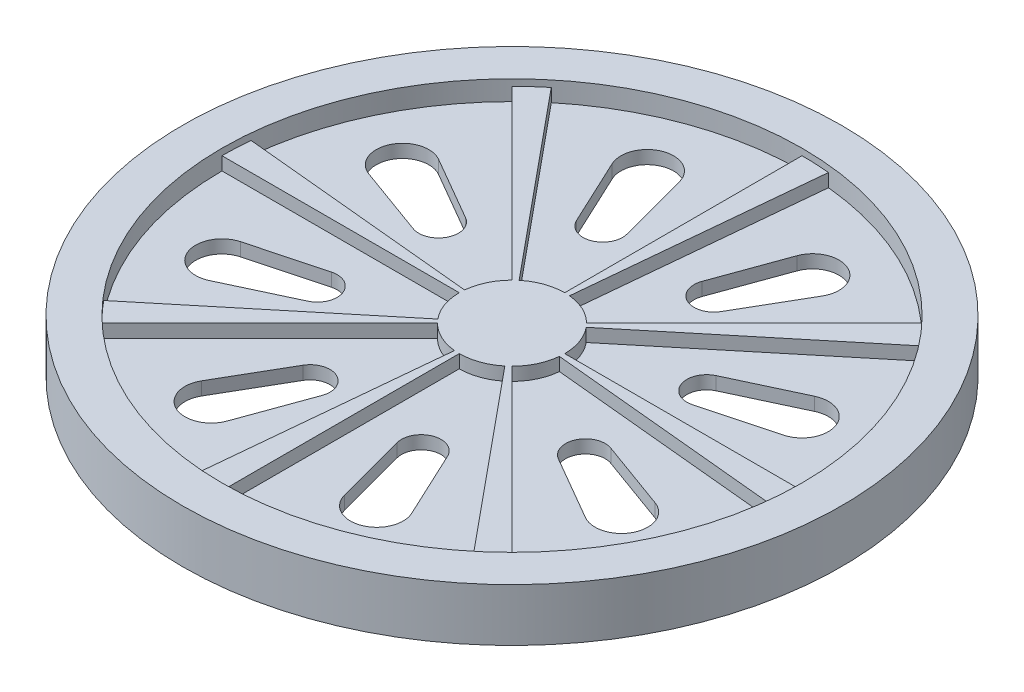
SolidWorks part; units mm, degrees
ref_plane "Front Plane" through (0, 0, 0) normal (0, 0, 1) x (1, 0, 0)
ref_plane "Top Plane" through (0, 0, 0) normal (0, 1, 0) x (1, 0, 0)
ref_plane "Right Plane" through (0, 0, 0) normal (1, 0, 0) x (0, 0, -1)
sketch "Sketch1" plane through (0, 0, 0) normal (0, 1, 0) x (1, 0, 0)
  line L0 (0, 4) -> (0, 22)
  line L1 (0.3831, 3.9816) -> (2.107, 21.8989)
  line L2 (3.0863, 2.5445) -> (16.9747, 13.995)
  line L3 (2.8284, 2.8284) -> (15.5563, 15.5563)
  line L4 (4, 0) -> (22, 0)
  line L5 (2.8284, -2.8284) -> (15.5563, -15.5563)
  line L6 (0, -4) -> (0, -22)
  line L7 (-2.8284, -2.8284) -> (-15.5563, -15.5563)
  line L8 (-4, 0) -> (-22, 0)
  line L9 (-2.8284, 2.8284) -> (-15.5563, 15.5563)
  line L10 (3.9816, -0.3831) -> (21.8989, -2.107)
  line L11 (2.5445, -3.0863) -> (13.995, -16.9747)
  line L12 (-0.3831, -3.9816) -> (-2.107, -21.8989)
  line L13 (-3.0863, -2.5445) -> (-16.9747, -13.995)
  line L14 (-3.9816, 0.3831) -> (-21.8989, 2.107)
  line L15 (-2.5445, 3.0863) -> (-13.995, 16.9747)
  line L17 (3.4591, 10.9535) -> (5.3757, 16.2376)
  line L18 (6.1674, 9.6906) -> (8.9833, 14.5554)
  line L20 (10.1912, 5.2993) -> (15.2829, 7.6806)
  line L21 (11.2133, 2.4913) -> (16.6444, 3.94)
  line L22 (10.9535, -3.4591) -> (16.2376, -5.3757)
  line L23 (9.6906, -6.1674) -> (14.5554, -8.9833)
  line L24 (5.2993, -10.1912) -> (7.6806, -15.2829)
  line L25 (2.4913, -11.2133) -> (3.94, -16.6444)
  line L26 (-3.4591, -10.9535) -> (-5.3757, -16.2376)
  line L27 (-6.1674, -9.6906) -> (-8.9833, -14.5554)
  line L28 (-10.1912, -5.2993) -> (-15.2829, -7.6806)
  line L29 (-11.2133, -2.4913) -> (-16.6444, -3.94)
  line L30 (-10.9535, 3.4591) -> (-16.2376, 5.3757)
  line L31 (-9.6906, 6.1674) -> (-14.5554, 8.9833)
  line L32 (-5.2993, 10.1912) -> (-7.6806, 15.2829)
  line L33 (-2.4913, 11.2133) -> (-3.94, 16.6444)
  circle A0 centre (0, 0) radius 25
  circle A1 centre (0, 0) radius 22
  circle A2 centre (0, 0) radius 4
  arc A3 (8.9833, 14.5554) -> (5.3757, 16.2376) centre (7.254, 15.5563) ccw
  arc A4 (3.4591, 10.9535) -> (6.1674, 9.6906) centre (4.8692, 10.442) ccw
  arc A5 (16.6444, 3.94) -> (15.2829, 7.6806) centre (16.1294, 5.8706) ccw
  arc A6 (10.1912, 5.2993) -> (11.2133, 2.4913) centre (10.8267, 3.9406) ccw
  arc A7 (14.5554, -8.9833) -> (16.2376, -5.3757) centre (15.5563, -7.254) ccw
  arc A8 (10.9535, -3.4591) -> (9.6906, -6.1674) centre (10.442, -4.8692) ccw
  arc A9 (3.94, -16.6444) -> (7.6806, -15.2829) centre (5.8706, -16.1294) ccw
  arc A10 (5.2993, -10.1912) -> (2.4913, -11.2133) centre (3.9406, -10.8267) ccw
  arc A11 (-8.9833, -14.5554) -> (-5.3757, -16.2376) centre (-7.254, -15.5563) ccw
  arc A12 (-3.4591, -10.9535) -> (-6.1674, -9.6906) centre (-4.8692, -10.442) ccw
  arc A13 (-16.6444, -3.94) -> (-15.2829, -7.6806) centre (-16.1294, -5.8706) ccw
  arc A14 (-10.1912, -5.2993) -> (-11.2133, -2.4913) centre (-10.8267, -3.9406) ccw
  arc A15 (-14.5554, 8.9833) -> (-16.2376, 5.3757) centre (-15.5563, 7.254) ccw
  arc A16 (-10.9535, 3.4591) -> (-9.6906, 6.1674) centre (-10.442, 4.8692) ccw
  arc A17 (-3.94, 16.6444) -> (-7.6806, 15.2829) centre (-5.8706, 16.1294) ccw
  arc A18 (-5.2993, 10.1912) -> (-2.4913, 11.2133) centre (-3.9406, 10.8267) ccw
  point P19 (0, 0)
  point P24 (0, 0)
  point P43 (0, 0)
  point P94 (0, 0)
  dimension "D1" = 50
  dimension "D2" = 8
  dimension "D5" = 8
  dimension "D4" = 8
extrude "Boss-Extrude2" add sketch "Sketch1" along normal blind 2 and the other way blind 2 contours A1 | A0
extrude "Boss-Extrude3" add sketch "Sketch1<5>" along normal blind 1.5 and the other way blind 1.5 contours A2 L1 A1 L0 | A2 L2 A1 L3 | A2 L10 A1 L4 | A2 L15 A1 L9 | A2 | A2 L14 A1 L8 | A2 L13 A1 L7 | A2 L12 A1 L6 | A2 L11 A1 L5 region at (0.7225, 0, -15.0538) region at (0, 0, 0) region at (-10.1337, 0, -11.1556) region at (11.1556, 0, -10.1337) region at (-15.0538, 0, -0.7225) region at (15.0538, 0, 0.7225) region at (-11.1556, 0, 10.1337) region at (10.1337, 0, 11.1556) region at (-0.7225, 0, 15.0538)
sketch "Sketch1<5>" plane through (0, 0, 0) normal (0, 1, 0) x (1, 0, 0) same geometry as "Sketch1"
extrude "Boss-Extrude5" add sketch "Sketch1<7>" along normal blind 0.5 and the other way blind 0.5 contours A2 L3 A1 L1 A4 L17 A3 L18 | A2 L0 A1 L15 A18 L32 A17 L33 | A2 L9 A1 L14 A16 L30 A15 L31 | A2 L8 A1 L13 A14 L28 A13 L29 | A2 L7 A1 L12 A12 L26 A11 L27 | A2 L5 A1 L10 A8 L22 A7 L23 | A2 L6 A1 L11 A10 L24 A9 L25 | A2 L4 A1 L2 A6 L20 A5 L21 region at (-1.4313, 0, -3.9861) region at (1.4876, 0, -12.9169) region at (-3.8383, 0, -1.8101) region at (10.1802, 0, -8.0882) region at (-3.9861, 0, 1.4313) region at (12.9169, 0, 1.4876) region at (-1.8101, 0, 3.8383) region at (8.0882, 0, 10.1802)
sketch "Sketch1<7>" plane through (0, 0, 0) normal (0, 1, 0) x (1, 0, 0) same geometry as "Sketch1"
